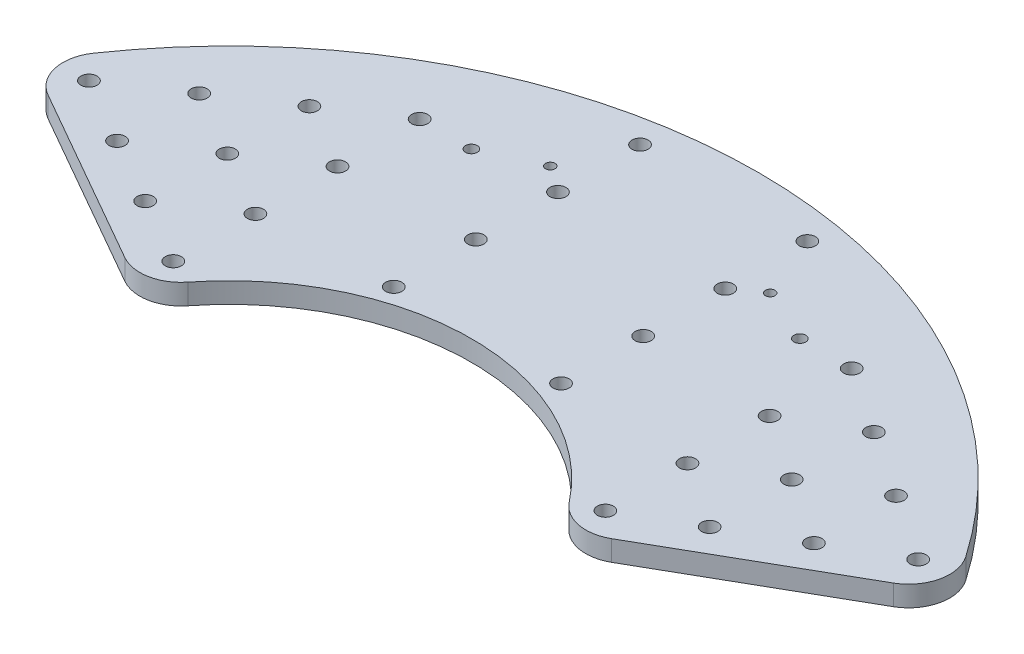
SolidWorks part; units mm, degrees
material "ABS"
ref_plane "Front Plane" through (0, 0, 0) normal (0, 0, 1) x (1, 0, 0)
ref_plane "Top Plane" through (0, 0, 0) normal (0, 1, 0) x (1, 0, 0)
ref_plane "Right Plane" through (0, 0, 0) normal (1, 0, 0) x (0, 0, -1)
sketch "Sketch1" plane through (0, 0, 0) normal (0, 1, 0) x (1, 0, 0)
  line L0 (0, 0) -> (0, 163.83) construction
  line L1 (0, 0) -> (0, 106.172) construction
  line L2 (-50.8, 106.172) -> (50.8, 106.172) construction
  line L3 (0, 163.83) -> (0, 74.93) construction
  line L4 (65.0581, 37.1746) -> (142.2457, 81.28)
  line L5 (-65.0581, 37.1746) -> (-142.2457, 81.28)
  arc A0 (-142.2457, 81.28) -> (142.2457, 81.28) centre (0, 0) cw
  arc A1 (-65.0581, 37.1746) -> (65.0581, 37.1746) centre (0, 0) cw
  dimension "D1" = 163.83
  dimension "D4" = 74.93
  dimension "D2" = 106.172
  dimension "D3" = 50.8
  dimension "D5" = 88.9
  dimension "D6" = 24.892
extrude "Boss-Extrude1" add sketch "Sketch1" along normal blind 6.35
ref_axis "Axis1" through (0, 6.35, -52.1043) along (0, 0, -1)
ref_point "Point1"
hole_wizard "#6 Clearance Hole1" positions "3DSketch1" profile "Sketch2" hole size "#6" standard "Ansi Inch"
sketch3d "3DSketch1"
  line L0 (0, 6.35, -74.93) -> (0, 6.35, -125.73) construction
  line L1 (0, 6.35, -52.1043) -> (0, 6.35, -180.2482) construction
  line L3 (50.8, 6.35, -125.73) -> (-50.8, 6.35, -125.73) construction
  arc A0 (-65.0581, 6.35, -37.1746) -> (65.0581, 6.35, -37.1746) centre (0, 6.35, 0) ccw construction
  point P12 (0, -68.58, 0)
  point P28 (-50.8, 6.35, -125.73)
  point P30 (50.8, 6.35, -125.73)
  dimension "D1" = 50.8
  dimension "D2" = 101.6
  dimension "D3" = 50.8
sketch "Sketch2" plane through (-50.8, 6.35, -125.73) normal (1, 0, 0) x (0, 0, 1)
  line L0 (0, 0) -> (0, 26.4989)
  line L1 (0, 26.4989) -> (1.8288, 25.4)
  line L2 (1.8288, 25.4) -> (1.8288, 0)
  line L5 (1.8288, 0) -> (0, 0)
  line L10 (0, 26.4989) -> (-1.8288, 25.4) construction
  line L11 (0, -6.35) -> (0, 107.95) construction
  dimension "Hole Dia." = 3.6576
  dimension "Hole Depth" = 25.4
  dimension "Drill Angle" = 118
fillet "Fillet1" radius 12.7 4 edges at (65.0581, 3.175, -37.1746) (-142.2457, 3.175, -81.28) (-65.0581, 3.175, -37.1746) (142.2457, 3.175, -81.28)
hole_wizard "#4 Clearance Hole1" positions "Sketch4" profile "Sketch3" hole size "#4" standard "Ansi Inch"
sketch "Sketch4" plane through (0, 6.35, 0) normal (0, 1, 0) x (-1, 0, 0)
  line L0 (0, -52.1043) -> (0, -180.2482) construction
  line L1 (0, -163.83) -> (0, -80.1707) construction
  arc A0 (-134.9123, -92.9459) -> (134.9123, -92.9459) centre (0, 0) ccw construction
  point P0 (-34.0106, -133.35)
  point P4 (0, -163.83)
  point P14 (34.0106, -133.35)
  dimension "D1" = 34.0106
  dimension "D2" = 30.48
sketch "Sketch3" plane through (34.0106, 6.35, -133.35) normal (1, 0, 0) x (0, 0, 1)
  line L0 (0, 0) -> (0, 26.2852)
  line L1 (0, 26.2852) -> (1.4732, 25.4)
  line L2 (1.4732, 25.4) -> (1.4732, 0)
  line L5 (1.4732, 0) -> (0, 0)
  line L10 (0, 26.2852) -> (-1.4732, 25.4) construction
  line L11 (0, -6.35) -> (0, 107.95) construction
  dimension "Hole Dia." = 2.9464
  dimension "Hole Depth" = 25.4
  dimension "Drill Angle" = 118
hole_wizard "#10 Clearance Hole1" positions "Sketch6" profile "Sketch5" hole size "#10" standard "Ansi Inch"
sketch "Sketch6" plane through (0, 6.35, 0) normal (0, 1, 0) x (-1, 0, 0)
  line L0 (128.2551, -84.874) -> (130.7547, -74.714) construction
  line L2 (128.2551, -84.874) -> (134.9123, -92.9459) construction
  line L4 (75.2816, -43.0163) -> (69.8344, -34.44) construction
  line L5 (69.8344, -34.44) -> (66.5461, -34.44) construction
  arc A0 (-134.9123, -92.9459) -> (134.9123, -92.9459) centre (0, 0) ccw construction
  arc A1 (134.9123, -92.9459) -> (130.7547, -74.714) centre (124.454, -85.7408) ccw construction
  arc A2 (-58.9836, -46.2108) -> (58.9836, -46.2108) centre (0, 0) ccw construction
  point P0 (128.2551, -84.874)
  dimension "D1" = 10.16
  dimension "D2" = 10.16
sketch "Sketch5" plane through (-128.2551, 6.35, -84.874) normal (1, 0, 0) x (0, 0, 1)
  line L0 (0, 0) -> (0, 26.8957)
  line L1 (0, 26.8957) -> (2.4892, 25.4)
  line L2 (2.4892, 25.4) -> (2.4892, 0)
  line L5 (2.4892, 0) -> (0, 0)
  line L10 (0, 26.8957) -> (-2.4892, 25.4) construction
  line L11 (0, -6.35) -> (0, 107.95) construction
  dimension "Hole Dia." = 4.9784
  dimension "Hole Depth" = 25.4
  dimension "Drill Angle" = 118
ref_point "Point3"
sketch "Sketch7" plane through (0, 6.35, 0) normal (0, 1, 0) x (-1, 0, 0)
  line L0 (75.2816, -43.0163) -> (68.2586, -50.3582) construction
  line L1 (68.2586, -50.3582) -> (58.9836, -46.2108) construction
  dimension "D1" = 10.16
ref_axis "Axis4" through (-128.2551, 6.35, -84.874) along (0.8668, 0, 0.4987)
pattern_linear "LPattern4" count 6 spacing 25.4 along (0, 0, -1) count 7 spacing 23.622 along (0.8668, 0, 0.4987) skipping (0, 4), (0, 5), (0, 6), (1, 0), (1, 4), (1, 5), (1, 6), (2, 0), (2, 1), (2, 4), (2, 6), (3, 0), (3, 1), (3, 2), (3, 4), (3, 6), (4, 0), (4, 1), (4, 2), (4, 3), (4, 4), (4, 6), (5, 0), (5, 1), (5, 2), (5, 3), (5, 4), (5, 6) of "#10 Clearance Hole1"
ref_plane "Plane1" through (0, 0, 0) normal (1, 0, 0) x (0, 0, -1)
mirror "Mirror4" about plane through (0, 0, 0) normal (1, 0, 0) of "LPattern4"
